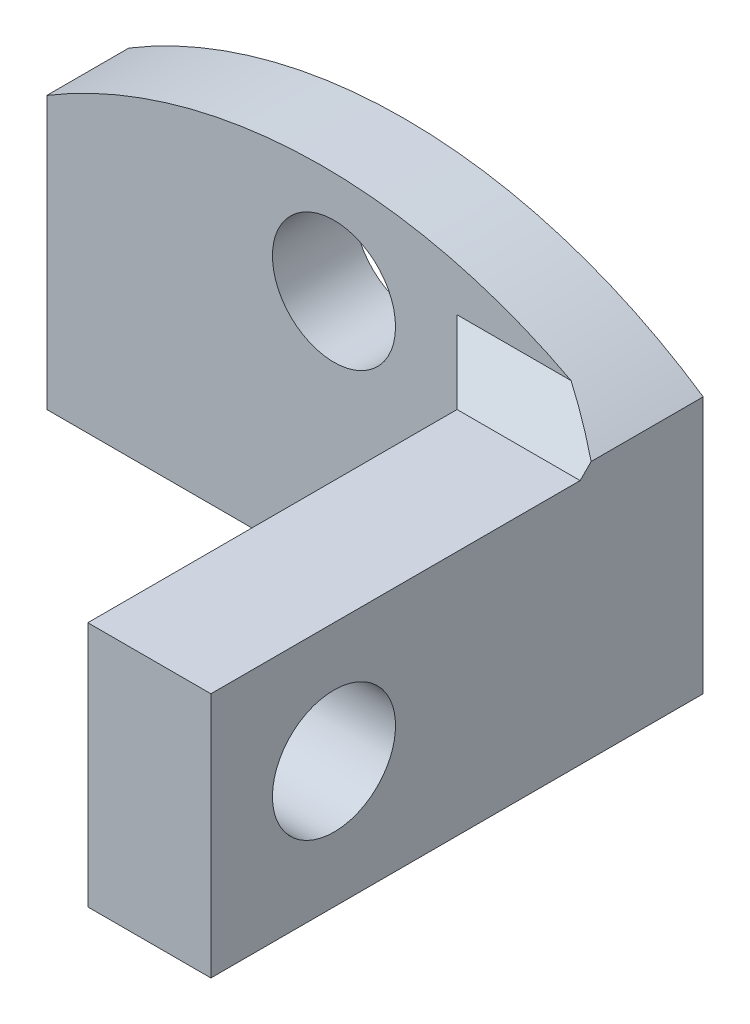
SolidWorks part; units mm, degrees
ref_plane "Płaszczyzna przednia" through (0, 0, 0) normal (0, 0, 1) x (1, 0, 0)
ref_plane "Płaszczyzna górna" through (0, 0, 0) normal (0, 1, 0) x (1, 0, 0)
ref_plane "Płaszczyzna prawa" through (0, 0, 0) normal (1, 0, 0) x (0, 0, -1)
sketch "Szkic1" plane through (0, 0, 0) normal (0, 0, 1) x (1, 0, 0)
  line L1 (-6.7165, 4.5) -> (7.2835, 4.5)
  line L2 (-6.7165, 4.5) -> (-6.7165, 11.1305)
  line L4 (7.2835, 4.5) -> (7.2835, 10.7681)
  arc A0 (7.2835, 10.7681) -> (-6.7165, 11.1305) centre (0, 0) ccw
  circle A1 centre (0.2835, 10.4962) radius 1.5
  dimension "D1" = 26
  dimension "D2" = 3
  dimension "D3" = 2.5
  dimension "D4" = 8.5
  dimension "D6" = 7
extrude "Dodanie-wyciągnięcie1" add sketch "Szkic1" along normal blind 2
sketch "Szkic2" plane through (0, 0, 2) normal (0, 0, 1) x (1, 0, 0)
  line L1 (7.2835, 4.5) -> (4.2835, 4.5)
  line L2 (7.2835, 4.5) -> (7.2835, 10.5)
  line L3 (7.2835, 10.5) -> (4.2835, 10.5)
  line L4 (4.2835, 4.5) -> (4.2835, 10.5)
  dimension "D1" = 3
  dimension "D2" = 6
extrude "Dodanie-wyciągnięcie2" add sketch "Szkic2" along normal blind 10
sketch "Szkic3" plane through (4.2835, 0, 0) normal (-1, 0, 0) x (0, 0, 1)
  line L0 (12, 10.5) -> (12, 4.5) construction
  circle A0 centre (9, 7.5792) radius 1.5
  dimension "D2" = 3
  dimension "D1" = 3
extrude "Wytnij-wyciągnięcie1" cut sketch "Szkic3" against normal up to surface (3 mm away) up to face at (7.2835, 8.5894, 4.6667)
chamfer "Sfazowanie1" distance 1 angle 45 1 edges at (4.2835, 7.5, 2)
chamfer "Sfazowanie2" distance 1 angle 45 1 edges at (5.2835, 10.5, 2)
